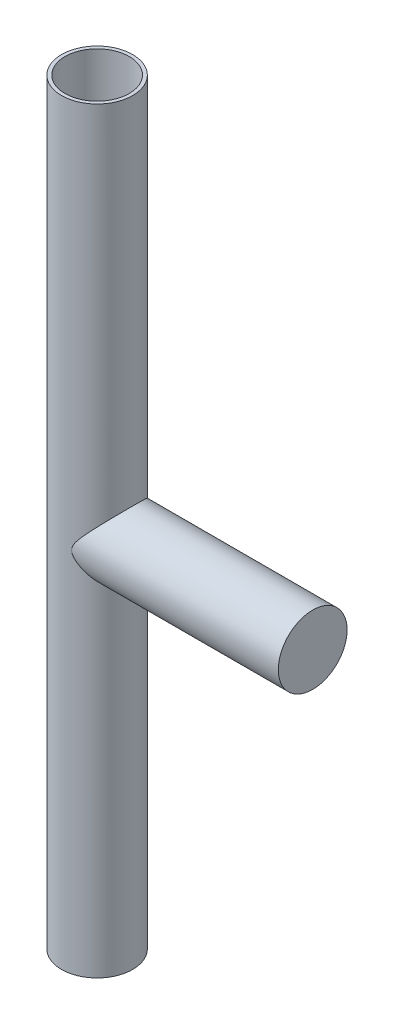
SolidWorks part; units mm, degrees
ref_plane "Front Plane" through (0, 0, 0) normal (0, 0, 1) x (1, 0, 0)
ref_plane "Top Plane" through (0, 0, 0) normal (0, 1, 0) x (1, 0, 0)
ref_plane "Right Plane" through (0, 0, 0) normal (1, 0, 0) x (0, 0, -1)
sketch "Sketch1" plane through (0, 0, 0) normal (0, 1, 0) x (1, 0, 0)
  circle A0 centre (0, 0) radius 7.75
  circle A1 centre (0, 0) radius 7
  dimension "D1" = 15.5
  dimension "D2" = 14
extrude "Boss-Extrude1" add sketch "Sketch1" along normal blind 160 and the other way blind 5
sketch "Sketch5" plane through (0, 0, 0) normal (1, 0, 0) x (0, 0, -1)
  circle A0 centre (0, 75) radius 7.5
  dimension "D1" = 15
extrude "Boss-Extrude3" add sketch "Sketch5" along normal blind 47
